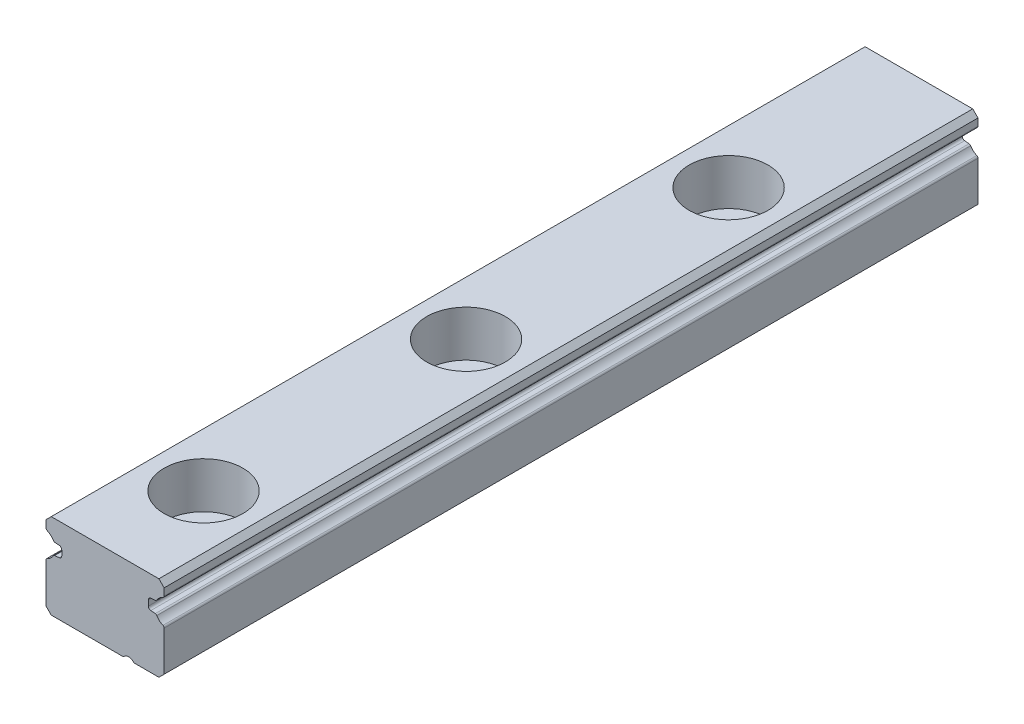
SolidWorks part; units mm, degrees
ref_plane "Front Plane" through (0, 0, 0) normal (0, 0, 1) x (1, 0, 0)
ref_plane "Top Plane" through (0, 0, 0) normal (0, 1, 0) x (1, 0, 0)
ref_plane "Right Plane" through (0, 0, 0) normal (1, 0, 0) x (0, 0, -1)
sketch "Sketch1" plane through (0, 0, 0) normal (0, 0, 1) x (1, 0, 0)
  line L0 (-4.5, 0) -> (4.5, 0) construction
  line L1 (0, -3.25) -> (0, 3.25) construction
  line L2 (0, 3.25) -> (0, -3.25) construction
  line L3 (-3, 3.25) -> (3, 3.25) construction
  line L4 (-1.75, -0.25) -> (1.75, -0.25) construction
  point P0 (0, -0.25)
  point P3 (-4.5, -3.25)
  point P4 (0, 0)
  point P8 (0, 0)
  point P11 (0, 3.25)
  point P15 (0, 3.25)
  point P17 (0, -0.25)
  point P18 (4.5, 3.25)
  point P20 (-4.5, 3.25)
  dimension "Rail Width" = 9
  dimension "Rail Height" = 6.5
  dimension "Mounting Hole Depth" = 3
  dimension "Mounting Hole Counterbore Diameter" = 6
  dimension "Mounting Hole Diameter" = 3.5
sketch "Sketch2" plane through (0, 0, 0) normal (1, 0, 0) x (0, 0, -1)
  line L0 (31, 0) -> (-31, 0) construction
  line L1 (-1.5, 3.25) -> (1.5, 3.25) construction
  line L3 (0, 3.25) -> (0, 0) construction
  point P0 (-23.5, 0)
  point P4 (0, 0)
  point P5 (-3.5, 0)
  point P6 (-13.5, 0)
  point P9 (-23.5, 3.25)
  point P10 (0, 3.25)
  point P11 (31, 3.25)
  point P13 (-31, 3.25)
  point P14 (13.5, 0)
  point P17 (-31, -3.25)
  dimension "Rail Length" = 62
  dimension "Mounting Hole Center to Edge" = 7.5
  dimension "Mounting Hole Center to Center" = 20
  dimension "Number of Mounting Holes" = 3
  dimension "Break Line" = 10
sketch "Sketch3" plane through (0, 0, 0) normal (0, 0, 1) x (1, 0, 0)
  point P0 (0, 3.25)
  line B0 (-4.5, 0.1917) -> (-4.5, -2.85)
  line B1 (-4.5, -2.85) -> (-4.1, -3.25)
  line B2 (-4.1, -3.25) -> (1.4, -3.25)
  line B3 (2.2, -3.25) -> (4.1, -3.25)
  line B4 (4.1, -3.25) -> (4.5, -2.85)
  line B5 (4.5, -2.85) -> (4.5, 0.1917)
  line B6 (3.8235, 0.8135) -> (3.4826, 0.8434)
  line B7 (3.3, 1.0426) -> (3.3, 1.4574)
  line B8 (3.4826, 1.6566) -> (3.8235, 1.6865)
  line B9 (4.5, 2.3083) -> (4.5, 2.85)
  line B10 (4.5, 2.85) -> (4.1, 3.25)
  line B11 (4.1, 3.25) -> (-4.1, 3.25)
  line B12 (-4.1, 3.25) -> (-4.5, 2.85)
  line B13 (-4.5, 2.85) -> (-4.5, 2.3083)
  line B14 (-3.8235, 1.6865) -> (-3.4826, 1.6566)
  line B15 (-3.3, 1.4574) -> (-3.3, 1.0426)
  line B16 (-3.4826, 0.8434) -> (-3.8235, 0.8135)
  arc B17 (2.2, -3.25) -> (1.4, -3.25) centre (1.8, -3.55) ccw
  arc B18 (4.5, 0.1917) -> (4.4087, 0.3297) centre (4.35, 0.1917) ccw
  arc B19 (3.9395, 0.7405) -> (4.4087, 0.3297) centre (4.8, 1.25) ccw
  arc B20 (3.9395, 0.7405) -> (3.8235, 0.8135) centre (3.8104, 0.6641) ccw
  arc B21 (3.3, 1.0426) -> (3.4826, 0.8434) centre (3.5, 1.0426) ccw
  arc B22 (3.4826, 1.6566) -> (3.3, 1.4574) centre (3.5, 1.4574) ccw
  arc B23 (3.8235, 1.6865) -> (3.9395, 1.7595) centre (3.8104, 1.8359) ccw
  arc B24 (4.4087, 2.1703) -> (3.9395, 1.7595) centre (4.8, 1.25) ccw
  arc B25 (4.4087, 2.1703) -> (4.5, 2.3083) centre (4.35, 2.3083) ccw
  arc B26 (-4.5, 2.3083) -> (-4.4087, 2.1703) centre (-4.35, 2.3083) ccw
  arc B27 (-3.9395, 1.7595) -> (-4.4087, 2.1703) centre (-4.8, 1.25) ccw
  arc B28 (-3.9395, 1.7595) -> (-3.8235, 1.6865) centre (-3.8104, 1.8359) ccw
  arc B29 (-3.3, 1.4574) -> (-3.4826, 1.6566) centre (-3.5, 1.4574) ccw
  arc B30 (-3.4826, 0.8434) -> (-3.3, 1.0426) centre (-3.5, 1.0426) ccw
  arc B31 (-3.8235, 0.8135) -> (-3.9395, 0.7405) centre (-3.8104, 0.6641) ccw
  arc B32 (-4.4087, 0.3297) -> (-3.9395, 0.7405) centre (-4.8, 1.25) ccw
  arc B33 (-4.4087, 0.3297) -> (-4.5, 0.1917) centre (-4.35, 0.1917) ccw
sketch_block_instance "9mm Block-1"
sketch_block "9mm Block"
extrude "Boss-Extrude1" add sketch "Sketch3" against normal up to vertex (31 mm away) from vertex up to point (0, 0, -31) starting at point (0, 0, 31)
ref_plane "Plane1" through (0, 0, 23.5) normal (0, 0, 1) x (1, 0, 0)
sketch "Sketch4" plane through (0, 0, 23.5) normal (0, 0, 1) x (1, 0, 0)
  line L0 (0, 3.25) -> (0, -3.25)
  line L1 (0, -3.25) -> (-1.75, -3.25)
  line L3 (-1.75, -3.25) -> (-1.75, -0.25)
  line L4 (-1.75, -0.25) -> (-3, -0.25)
  line L5 (-3, -0.25) -> (-3, 3.25)
  line L6 (-3, 3.25) -> (0, 3.25)
revolve "Cut-Revolve1" cut sketch "Sketch4" angle 360 about L0
sketch "Sketch6" plane through (0, 0, 0) normal (1, 0, 0) x (0, 0, -1)
  line L0 (-20.5, -0.25) -> (-26.5, -0.25) construction
  line L5 (-20.5, -0.25) -> (-26.5, -0.25)
  line L17 (-25.25, -0.25) -> (-25.25, -3.25) construction
  line L18 (-21.75, -3.25) -> (-21.75, -0.25) construction
  line L32 (-20.5, -0.25) -> (-20.5, 3.25) construction
  line L33 (-26.5, 3.25) -> (-26.5, -0.25) construction
  line L34 (-25.25, -0.25) -> (-25.25, -3.25)
  line L35 (-21.75, -3.25) -> (-21.75, -0.25)
  line L36 (-20.5, -0.25) -> (-20.5, 3.25)
  line L37 (-26.5, 3.25) -> (-26.5, -0.25)
  line L38 (0, 3.25) -> (0, -3.25) construction
  line L40 (26.5, 3.25) -> (26.5, -0.25)
  line L41 (20.5, -0.25) -> (20.5, 3.25)
  line L42 (21.75, -3.25) -> (21.75, -0.25)
  line L43 (25.25, -0.25) -> (25.25, -3.25)
  line L44 (20.5, -0.25) -> (26.5, -0.25)
sketch "Sketch7" plane through (0, 0, 0) normal (0, 0, 1) x (1, 0, 0)
  line L0 (3, -0.25) -> (3, 3.25) construction
  line L1 (-3, 3.25) -> (-3, -0.25) construction
  line L2 (3, -0.25) -> (3, 3.25)
  line L3 (-3, 3.25) -> (-3, -0.25)
  line L4 (1.75, -3.0525) -> (1.75, -0.25) construction
  line L11 (1.75, -3.0525) -> (1.75, -0.25)
  line L18 (-1.75, -0.25) -> (-1.75, -3.25) construction
  line L32 (3, -0.25) -> (-3, -0.25) construction
  line L34 (-1.75, -0.25) -> (-1.75, -3.25)
  line L37 (3, -0.25) -> (-3, -0.25)
pattern_linear "LPattern1" count 3 spacing 20 along (0, 0, -1) of "Cut-Revolve1"
equation "\"D3@LPattern1\"=\"Mounting Hole Center to Center@Sketch2\""
equation "\"Break Line@Sketch2\"=\"Mounting Hole Center to Center@Sketch2\"/2"
